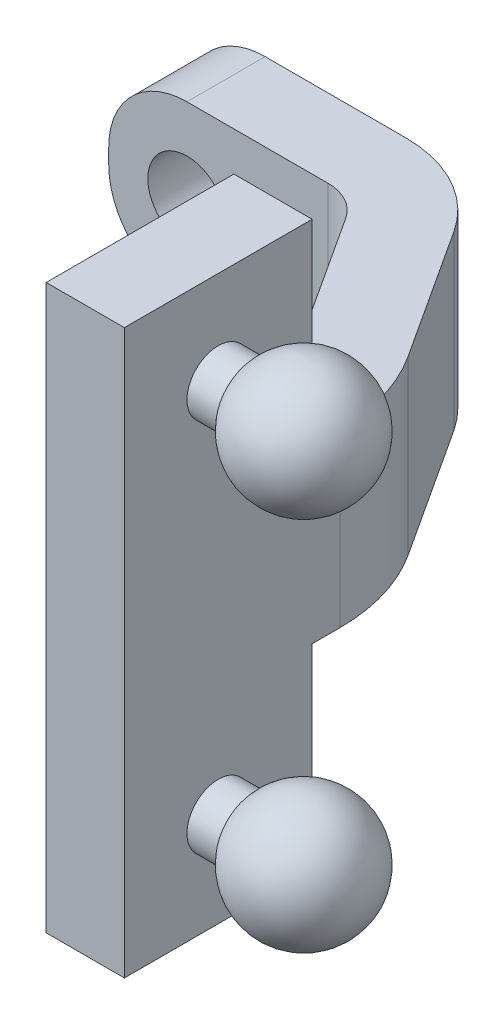
SolidWorks part; units mm, degrees
ref_plane "前视基准面" through (0, 0, 0) normal (0, 0, 1) x (1, 0, 0)
ref_plane "上视基准面" through (0, 0, 0) normal (0, 1, 0) x (1, 0, 0)
ref_plane "右视基准面" through (0, 0, 0) normal (1, 0, 0) x (0, 0, -1)
other "Configuration Table"
sketch "草图1" plane through (0, 0, 0) normal (0, 1, 0) x (1, 0, 0)
  line L0 (0, 0) -> (7, 0)
  line L1 (14, -9.1042) -> (14, -16)
  line L2 (0, -2.5) -> (7, -2.5)
  line L3 (11.5, -9.1042) -> (11.5, -16)
  line L4 (11.5, -16) -> (14, -16)
  line L5 (0, 0) -> (0, -2.5)
  line L6 (10.3535, -1.8196) -> (13.0862, -6.0224)
  line L7 (8.2575, -3.1823) -> (10.9903, -7.3852)
  arc A0 (7, 0) -> (10.3535, -1.8196) centre (7, -4) cw
  arc A3 (7, -2.5) -> (8.2575, -3.1823) centre (7, -4) cw
  arc A6 (9.6623, -0.4928) -> (14, -9.1042) centre (3.2834, -9.1042) cw construction
  arc A7 (10.3535, -1.8196) -> (9.6623, -0.4928) centre (16.8788, 2.4233) ccw construction
  arc A8 (8.2575, -3.1823) -> (7.6722, -2.1578) centre (16.8788, 2.4233) ccw construction
  arc A9 (7.6722, -2.1578) -> (11.5, -9.1042) centre (3.2834, -9.1042) cw construction
  arc A10 (13.0862, -6.0224) -> (14, -9.1042) centre (8.3466, -9.1042) cw
  arc A11 (11.5, -9.1042) -> (10.9903, -7.3852) centre (8.3466, -9.1042) ccw
  dimension "D1" = 2.5
  dimension "D3" = 4
  dimension "D4" = 14
  dimension "D2" = 7
  dimension "D6" = 16
extrude "凸台-拉伸1" add sketch "草图1" along normal mid plane 5.5
sketch "草图2" plane through (0, 0, 0) normal (0, 0, -1) x (-1, 0, 0)
  line L0 (0, 2.75) -> (0, -2.75) construction
  circle A0 centre (-2.5, 0) radius 1.25
  point P5 (0, 0)
  dimension "D1" = 2.5
  dimension "D2" = 2.5
extrude "切除-拉伸1" cut sketch "草图2" against normal blind 10
fillet "圆角2" radius 2.5 2 edges at (0, -2.75, 1.25) (0, 2.75, 1.25)
sketch "草图4" plane through (11.5, 0, 0) normal (-1, 0, 0) x (0, 0, 1)
  line L0 (16, 2.75) -> (16, -2.75) construction
  line L1 (10, 9) -> (16, 9)
  line L2 (10, 9) -> (10, -9)
  line L3 (10, -9) -> (16, -9)
  line L4 (16, 9) -> (16, -9)
  line L5 (10, 9) -> (16, -9) construction
  line L6 (10, -9) -> (16, 9) construction
  point P0 (13, 0)
  dimension "D1" = 18
  dimension "D2" = 6
extrude "凸台-拉伸2" add sketch "草图4" against normal up to surface (2.5 mm away) up to face at (14, 0, 12.5521)
sketch "草图5" plane through (14, 0, 0) normal (1, 0, 0) x (0, 0, -1)
  line L0 (-10, 9) -> (-16, 9) construction
  line L1 (-10, 2.75) -> (-10, 9) construction
  circle A0 centre (-13, 6) radius 1
  dimension "D1" = 2
  dimension "D2" = 3
  dimension "D3" = 3
extrude "凸台-拉伸3" add sketch "草图5" along normal blind 1
ref_axis "基准轴1" through (15, 6, 13) along (-1, 0, 0)
ref_plane "基准面1" through (0, 0, 13) normal (0, 0, -1) x (-1, 0, 0)
sketch "草图6" plane through (0, 0, 13) normal (0, 0, -1) x (-1, 0, 0)
  line L0 (-15, 6) -> (-18.7321, 6)
  line L1 (-15, 7) -> (-15, 5) construction
  line L2 (-15, 6) -> (-14, 6) construction
  line L3 (-15, 6) -> (-15, 7)
  line L4 (-14, 7) -> (-15, 7) construction
  arc A0 (-15, 7) -> (-18.7321, 6) centre (-16.7321, 6) ccw
  dimension "D1" = 4
revolve "旋转1" add sketch "草图6" angle 360 about L0
mirror "镜向1" about plane through (0, 0, 0) normal (0, 1, 0) of "凸台-拉伸3", "旋转1"
